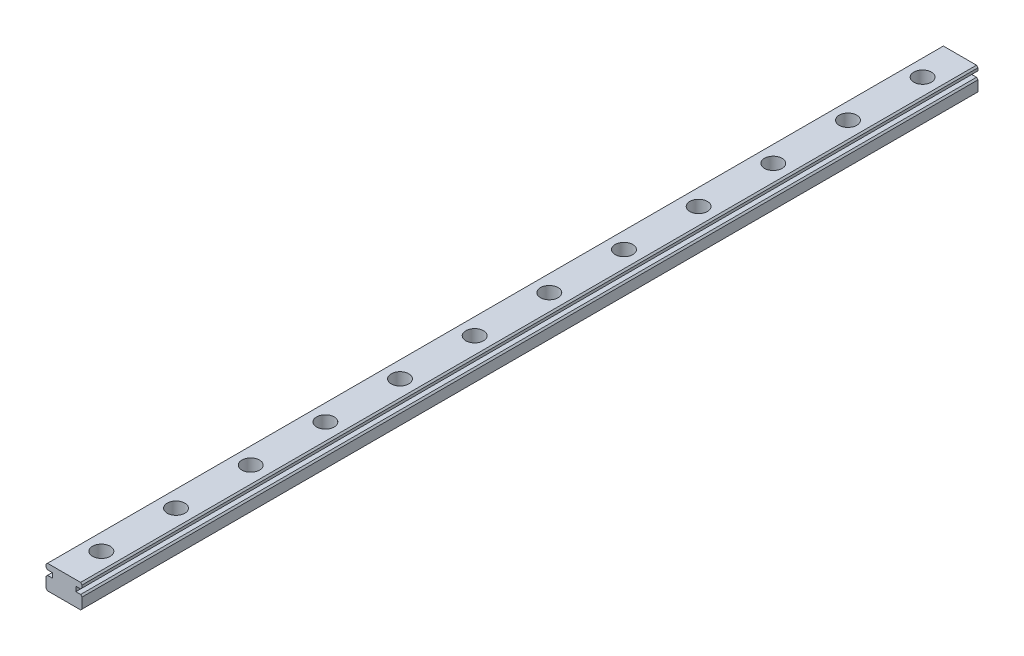
SolidWorks part; units mm, degrees
ref_plane "Front Plane" through (0, 0, 0) normal (0, 0, 1) x (1, 0, 0)
ref_plane "Top Plane" through (0, 0, 0) normal (0, 1, 0) x (1, 0, 0)
ref_plane "Right Plane" through (0, 0, 0) normal (1, 0, 0) x (0, 0, -1)
sketch "Sketch1" plane through (0, 0, 0) normal (0, 0, 1) x (1, 0, 0)
  line L0 (6.05, 2.1) -> (3.95, 2.1)
  line L1 (-6.05, 4) -> (6.05, 4)
  line L2 (-6.05, 4) -> (-6.05, 2.1)
  line L3 (-6.05, -4) -> (6.05, -4)
  line L4 (6.05, 4) -> (6.05, 2.1)
  line L5 (-6.05, 4) -> (6.05, -4) construction
  line L6 (-6.05, -4) -> (6.05, 4) construction
  line L7 (3.95, 2.1) -> (3.95, 0.5)
  line L8 (3.95, 0.5) -> (6.05, 0.5)
  line L9 (0, 0) -> (0, 2.5782)
  line L10 (-3.95, 0.5) -> (-6.05, 0.5)
  line L11 (-3.95, 2.1) -> (-3.95, 0.5)
  line L12 (-6.05, 2.1) -> (-3.95, 2.1)
  line L13 (-6.05, 0.5) -> (-6.05, -4)
  line L14 (6.05, 0.5) -> (6.05, -4)
  point P0 (0, 0)
  dimension "D1" = 12.1
  dimension "D2" = 8
  dimension "D3" = 1.9
  dimension "D4" = 1.6
  dimension "D5" = 2.1
extrude "Boss-Extrude1" add sketch "Sketch1" along normal blind 300 contours L14 L8 L7 L0 L4 L1 L2 L12 L11 L10 L13 L3 region at (0, -0.097, 0)
chamfer "Chamfer1" distance 0.5 angle 45 8 edges at (6.05, -4, 150) (-6.05, -4, 150) (-6.05, 0.5, 150) (-6.05, 2.1, 150) (-6.05, 4, 150) (6.05, 4, 150) (6.05, 2.1, 150) (6.05, 0.5, 150)
sketch "Sketch2" plane through (0, 4, 0) normal (0, 1, 0) x (1, 0, 0)
  line L0 (5.55, -150) -> (-5.55, -150)
  line L1 (5.55, -300) -> (5.55, 0) construction
  line L2 (-5.55, 0) -> (-5.55, -300) construction
  line L3 (-5.55, 0) -> (5.55, 0) construction
  circle A0 centre (0, -137.5) radius 2.95
  circle A1 centre (0, -162.5) radius 2.95
  dimension "D4" = 5.9
  dimension "D5" = 5.9
  dimension "D1" = 150
  dimension "D2" = 12.5
  dimension "D3" = 12.5
extrude "Cut-Extrude1" cut sketch "Sketch2" against normal blind 5.6 contours A1 | A0
pattern_linear "LPattern1" count 6 spacing 25 along (0, 0, 1) of "Cut-Extrude1"
pattern_linear "LPattern2" count 7 spacing 25 along (0, 0, -1) of "Cut-Extrude1"
sketch "Sketch3" plane through (0, 4, 0) normal (0, 1, 0) x (1, 0, 0)
  circle A0 centre (0, -162.5) radius 1.6
  circle A1 centre (0, -137.5) radius 1.6
  dimension "D1" = 3.2
  dimension "D2" = 3.2
extrude "Cut-Extrude2" cut sketch "Sketch3" against normal through all
pattern_linear "LPattern3" count 7 spacing 25 along (0, 0, -1) count 6 spacing 25 along (0, 0, 1) of "Cut-Extrude2"
equation "\"length\"= 300mm"
equation "\"D1@Sketch2\"=\"length\"/2"
equation "\"holeSpacing\"= 25mm"
equation "\"D2@Sketch2\"=\"holeSpacing\"/2"
equation "\"D3@Sketch2\"=\"holeSpacing\"/2"
equation "\"D3@LPattern1\"=\"holeSpacing\""
equation "\"D3@LPattern2\"=\"holeSpacing\""
equation "\"D3@LPattern3\"=\"holeSpacing\""
equation "\"D4@LPattern3\"=\"holeSpacing\""
equation "\"endDist\"= \"RD3@Annotations\""
equation "\"D1@Boss-Extrude1\"=\"length\""
